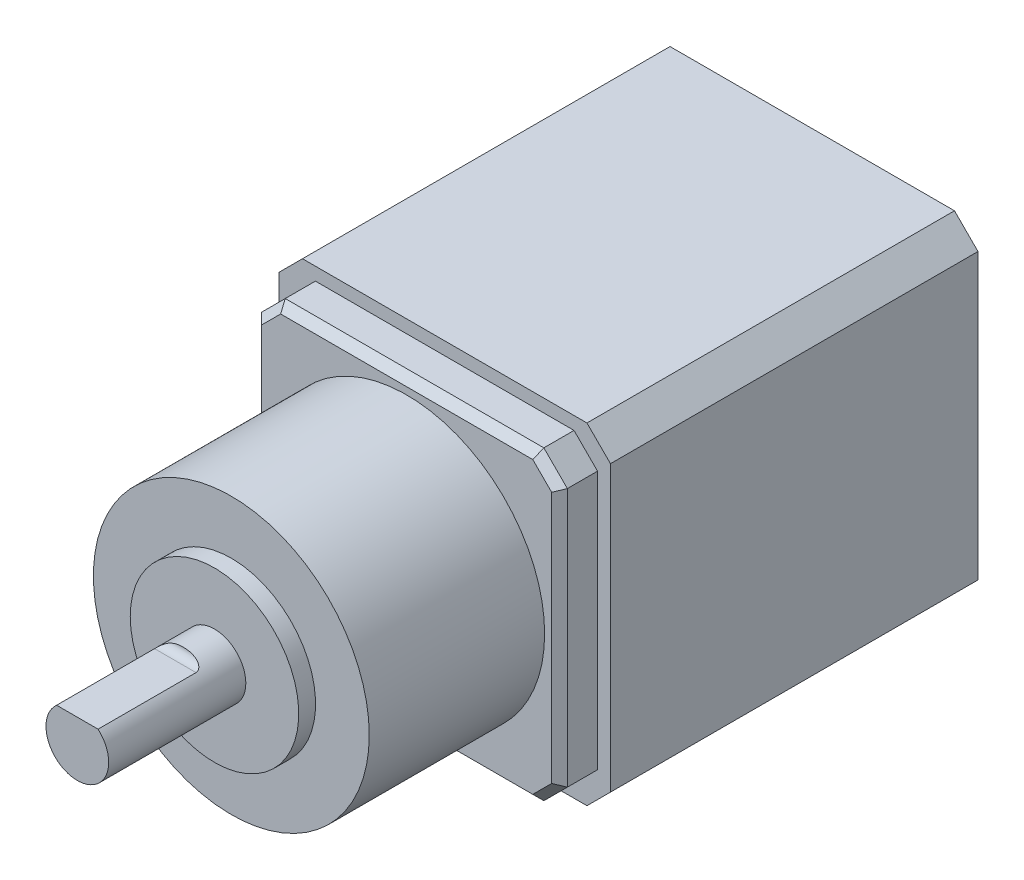
SolidWorks part; units mm, degrees
ref_plane "Front Plane" through (0, 0, 0) normal (0, 0, 1) x (1, 0, 0)
ref_plane "Top Plane" through (0, 0, 0) normal (0, 1, 0) x (1, 0, 0)
ref_plane "Right Plane" through (0, 0, 0) normal (1, 0, 0) x (0, 0, -1)
sketch "Sketch1" plane through (0, 0, 0) normal (0, 0, 1) x (1, 0, 0)
  line L1 (-21.15, -21.15) -> (21.15, -21.15)
  line L2 (-21.15, -21.15) -> (-21.15, 21.15)
  line L3 (-21.15, 21.15) -> (21.15, 21.15)
  line L4 (21.15, -21.15) -> (21.15, 21.15)
  line L5 (-21.15, -21.15) -> (21.15, 21.15) construction
  line L6 (-21.15, 21.15) -> (21.15, -21.15) construction
  point P0 (0, 0)
  dimension "D1" = 42.3
  dimension "D2" = 42.3
extrude "Boss-Extrude1" add sketch "Sketch1" along normal blind 46.9 contours L3 L4 L1 L2
sketch "Sketch2" plane through (0, 0, 46.9) normal (0, 0, 1) x (1, 0, 0)
  line L1 (-19.5, -19.5) -> (19.5, -19.5)
  line L2 (-19.5, -19.5) -> (-19.5, 19.5)
  line L3 (-19.5, 19.5) -> (19.5, 19.5)
  line L4 (19.5, -19.5) -> (19.5, 19.5)
  line L5 (-19.5, -19.5) -> (19.5, 19.5) construction
  line L6 (-19.5, 19.5) -> (19.5, -19.5) construction
  point P0 (0, 0)
  dimension "D1" = 39
extrude "Boss-Extrude2" add sketch "Sketch2" along normal blind 4.85
sketch "Sketch3" plane through (0, 0, 51.75) normal (0, 0, 1) x (1, 0, 0)
  circle A0 centre (0, 0) radius 17.6
  dimension "D1" = 35.2
extrude "Boss-Extrude3" add sketch "Sketch3" along normal blind 15.88
sketch "Sketch4" plane through (0, 0, 67.63) normal (0, 0, 1) x (1, 0, 0)
  circle A0 centre (0, 0) radius 17.6 construction
  circle A1 centre (0, 0) radius 17.6
extrude "Boss-Extrude4" add sketch "Sketch4" along normal blind 6.5
sketch "Sketch5" plane through (0, 0, 74.13) normal (0, 0, 1) x (1, 0, 0)
  circle A0 centre (0, 0) radius 10.75
  dimension "D1" = 21.5
extrude "Boss-Extrude5" add sketch "Sketch5" along normal blind 2.15
sketch "Sketch6" plane through (0, 0, 76.28) normal (0, 0, 1) x (1, 0, 0)
  circle A0 centre (0, 0) radius 4
  dimension "D1" = 8
extrude "Boss-Extrude6" add sketch "Sketch6" along normal blind 17.5
sketch "Sketch7" plane through (0, 0, 93.78) normal (0, 0, 1) x (1, 0, 0)
  line L0 (-2.6458, 3) -> (2.6458, 3)
  circle A0 centre (0, 0) radius 4 construction
  circle A2 centre (0, 0) radius 4
  circle M2 centre (0, 0) radius 4
  dimension "D1" = 7
extrude "Cut-Extrude1" cut sketch "Sketch7" against normal offset from surface (13.5 mm away) 4 contours L0 M2 region at (0, 3.4046, 93.78) up to face at (4, 0, 76.28)
chamfer "Chamfer1" distance 3 angle 45 8 edges at (-21.15, 21.15, 23.45) (-19.5, 19.5, 49.325) (-19.5, -19.5, 49.325) (-21.15, -21.15, 23.45) (21.15, -21.15, 23.45) (19.5, -19.5, 49.325) (19.5, 19.5, 49.325) (21.15, 21.15, 23.45)
chamfer "Chamfer2" distance 1 angle 45 8 edges at (18, 18, 51.75) (19.5, 0, 51.75) (18, -18, 51.75) (0, -19.5, 51.75) (-18, -18, 51.75) (-19.5, 0, 51.75) (-18, 18, 51.75) (0, 19.5, 51.75)
fillet "Fillet1" radius 1 1 edges at (0, 3, 80.28)
ref_axis "Shaft Axis" through (0, 0, 93.78) along (0, 0, -1)
